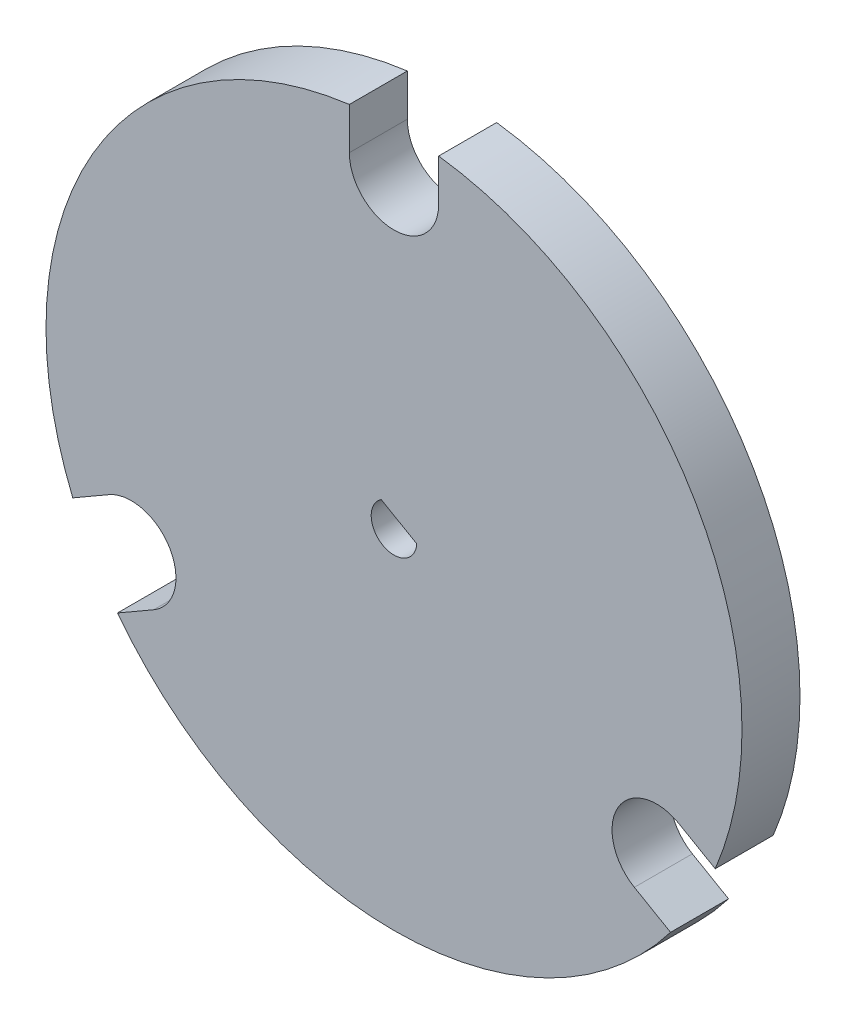
SolidWorks part; units mm, degrees
material "Acrylic (Medium-high impact)"
ref_plane "Front Plane" through (0, 0, 0) normal (0, 0, 1) x (1, 0, 0)
ref_plane "Top Plane" through (0, 0, 0) normal (0, 1, 0) x (1, 0, 0)
ref_plane "Right Plane" through (0, 0, 0) normal (1, 0, 0) x (0, 0, -1)
sketch "Sketch1" plane through (0, 0, 0) normal (0, 0, 1) x (1, 0, 0)
  circle A0 centre (0, 0) radius 38.1
  dimension "D1" = 76.2
extrude "Boss-Extrude1" add sketch "Sketch1" along normal blind 6.35
sketch "Sketch2" plane through (0, 0, 6.35) normal (0, 0, 1) x (1, 0, 0)
  line L0 (-4.8895, 33.2105) -> (-4.8895, 37.785)
  line L1 (0, 33.2105) -> (-28.7611, -16.6052) construction
  line L2 (-28.7611, -16.6052) -> (28.7611, -16.6052) construction
  line L3 (28.7611, -16.6052) -> (0, 33.2105) construction
  line L4 (4.8895, 33.2105) -> (4.8895, 37.785)
  line L5 (31.2059, -12.3708) -> (35.1675, -14.658)
  line L6 (26.3164, -20.8397) -> (30.278, -23.1269)
  line L7 (-26.3164, -20.8397) -> (-30.278, -23.1269)
  line L8 (-31.2059, -12.3708) -> (-35.1675, -14.658)
  circle A0 centre (0, 0) radius 16.6052 construction
  arc A1 (-4.8895, 33.2105) -> (4.8895, 33.2105) centre (0, 33.2105) ccw
  circle A2 centre (0, 0) radius 38.1 construction
  arc A3 (-4.8895, 37.785) -> (4.8895, 37.785) centre (0, 0) cw
  arc A4 (31.2059, -12.3708) -> (26.3164, -20.8397) centre (28.7611, -16.6052) ccw
  arc A5 (35.1675, -14.658) -> (30.278, -23.1269) centre (0, 0) cw
  arc A6 (-26.3164, -20.8397) -> (-31.2059, -12.3708) centre (-28.7611, -16.6053) ccw
  arc A7 (-30.278, -23.1269) -> (-35.1675, -14.658) centre (0, 0) cw
  point P25 (0, 0)
  dimension "D1" = 9.779
  dimension "D2" = 3
extrude "Cut-Extrude1" cut sketch "Sketch2" against normal through all
sketch "Sketch3" plane through (0, 0, 6.35) normal (0, 0, 1) x (1, 0, 0)
  line L2 (2.4934, -0.1813) -> (-1.4037, 2.0687)
  arc A1 (-1.4037, 2.0687) -> (2.4934, -0.1813) centre (0, 0) ccw
extrude "Cut-Extrude2" cut sketch "Sketch3" against normal through all
